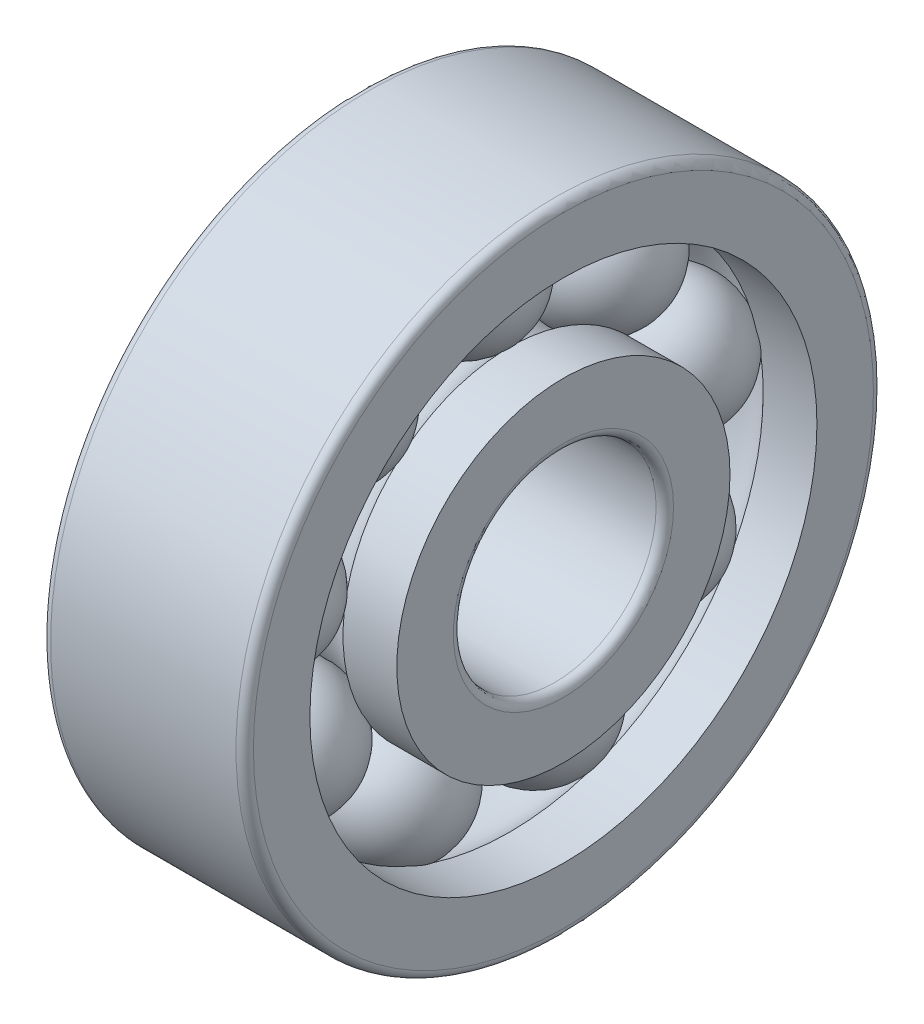
SolidWorks part; units mm, degrees
ref_plane "Plane1" through (0, 0, 0) normal (0, 0, 1) x (1, 0, 0)
ref_plane "Plane2" through (0, 0, 0) normal (0, 1, 0) x (1, 0, 0)
ref_plane "Plane3" through (0, 0, 0) normal (1, 0, 0) x (0, 0, -1)
sketch "Clipboard" plane through (0, 0, 0) normal (0, 0, 1) x (1, 0, 0)
  line L0 (-10, 0) -> (10, 0) construction
  line L1 (0, 0) -> (22.0854, -3.498)
  line L2 (0, 0) -> (7.2489, -0.1265)
  line L3 (0, 0) -> (22.3573, 0.3902)
  line L4 (0, 0) -> (-22.3573, -0.3902)
  dimension "BallCLRad" = 7.25
sketch "CagSpiSke" plane through (0, 0, 0) normal (0, 0, 1) x (1, 0, 0)
  line L0 (0.225, 6.875) -> (0.225, 7.625)
  line L1 (0.225, 7.625) -> (-0.225, 7.625)
  line L2 (-0.225, 7.625) -> (-0.225, 6.875)
  line L3 (-0.225, 6.875) -> (0.225, 6.875)
  line L4 (-20.6375, 0) -> (20.6375, 0) construction
  line L5 (0, 0) -> (0, 23.7692) construction
  dimension "OD" = 15.25
  dimension "ID" = 13.75
revolve "CageSpine" add sketch "CagSpiSke" angle 0.001 about L4 reverse direction yes
ref_axis "Axis1" through (-50, 0, 0) along (1, 0, 0)
sketch "CagBalSke" plane through (0, 0, 0) normal (0, 0, 1) x (1, 0, 0)
  line L0 (-2.475, 7.25) -> (2.475, 7.25)
  line L1 (-1.905, 7.25) -> (1.905, 7.25) construction
  line L2 (-10, 0) -> (10, 0) construction
  line L3 (0, 0) -> (0, 24) construction
  arc A0 (2.475, 7.25) -> (-2.475, 7.25) centre (0, 7.25) cw
  dimension "BallCLRad" = 7.25
revolve "CageBall" [suppressed] add sketch "CagBalSke" angle 360 about L1 reverse direction yes
pattern_circular "CageBalls" [suppressed] count 9 every 40 about axis through (-50, 0, 0) along (1, 0, 0)
sketch "CagTrmODSke" plane through (0, 0, 0) normal (0, 0, 1) x (1, 0, 0)
  line L0 (2.476, 7.625) -> (2.476, 9.726)
  line L1 (2.476, 9.726) -> (-2.476, 9.726)
  line L2 (-2.476, 9.726) -> (-2.476, 7.625)
  line L3 (-2.476, 7.625) -> (2.476, 7.625)
  line L4 (-20.6375, 0) -> (20.6375, 0) construction
  line L5 (0, 0) -> (0, 25) construction
  dimension "Width" = 4.952
  dimension "ID" = 15.25
  dimension "OD" = 19.452
revolve "CageTrimOD" [suppressed] cut sketch "CagTrmODSke" angle 360 about L4 reverse direction yes
sketch "CagTrmIDSke" plane through (0, 0, 0) normal (0, 0, 1) x (1, 0, 0)
  line L0 (2.476, 4.776) -> (2.476, 6.875)
  line L1 (2.476, 6.875) -> (-2.476, 6.875)
  line L2 (-2.476, 6.875) -> (-2.476, 4.776)
  line L3 (-2.476, 4.776) -> (2.476, 4.776)
  line L4 (-20.6375, 0) -> (20.6375, 0) construction
  line L5 (0, 0) -> (0, 25) construction
  dimension "Width" = 4.952
  dimension "ID" = 9.552
  dimension "OD" = 13.75
revolve "CageTrimID" [suppressed] cut sketch "CagTrmIDSke" angle 360 about L4 reverse direction yes
sketch "BalSimSke" plane through (0, 0, 0) normal (0, 0, 1) x (1, 0, 0)
  line L0 (-10, 0) -> (10, 0) construction
  line L1 (-10, 7.25) -> (10, 7.25) construction
  line L2 (0, 0) -> (0, 23) construction
  circle A0 centre (0, 7.25) radius 2.25
  dimension "BallCLRad" = 7.25
  dimension "Ball_diameter" = 4.5
revolve "BallsSimplified" [suppressed] add sketch "BalSimSke" angle 360 about L0
sketch "BalDetSke" plane through (0, 0, 0) normal (0, 0, 1) x (1, 0, 0)
  line L0 (-2.25, 7.25) -> (2.25, 7.25)
  line L1 (-1.905, 7.25) -> (1.905, 7.25) construction
  line L2 (0, 0) -> (0, 25) construction
  arc A0 (2.25, 7.25) -> (-2.25, 7.25) centre (0, 7.25) cw
  dimension "BallCLRad" = 7.25
  dimension "Ball_diameter" = 4.5
revolve "BallDetailed" add sketch "BalDetSke" angle 360 about L1 reverse direction yes
sketch "InnRacSke" plane through (0, 0, 0) normal (0, 0, 1) x (1, 0, 0)
  line L0 (-1.6434, 5.75) -> (-3.5, 5.75)
  line L1 (-3.5, 5.75) -> (-3.5, 3.8)
  line L2 (-3.2, 3.5) -> (3.2, 3.5)
  line L3 (3.5, 3.8) -> (3.5, 5.75)
  line L4 (3.5, 5.75) -> (1.6434, 5.75)
  line L5 (-20.6375, 0) -> (20.6375, 0) construction
  line L6 (0, 0) -> (0, 30) construction
  arc A0 (-3.5, 3.8) -> (-3.2, 3.5) centre (-3.2, 3.8) ccw
  arc A1 (3.2, 3.5) -> (3.5, 3.8) centre (3.2, 3.8) ccw
  arc A2 (1.6434, 5.75) -> (-1.6434, 5.75) centre (0, 7.25) cw
  dimension "BallCLRad" = 7.25
  dimension "Fillet_radius" = 0.3
  dimension "Ball_diameter" = 4.45
  dimension "ID" = 7
  dimension "OD" = 11.5
  dimension "Width" = 7
revolve "InnerRace" add sketch "InnRacSke" angle 360 about L5 reverse direction yes
sketch "OutRacSke" plane through (0, 0, 0) normal (0, 0, 1) x (1, 0, 0)
  line L0 (-1.6434, 8.75) -> (-3.5, 8.75)
  line L1 (-3.5, 8.75) -> (-3.5, 10.7)
  line L2 (-3.2, 11) -> (3.2, 11)
  line L3 (3.5, 10.7) -> (3.5, 8.75)
  line L4 (3.5, 8.75) -> (1.6434, 8.75)
  line L5 (-20.6375, 0) -> (20.6375, 0) construction
  line L6 (0, 0) -> (0, 30) construction
  arc A0 (-3.5, 10.7) -> (-3.2, 11) centre (-3.2, 10.7) cw
  arc A1 (3.2, 11) -> (3.5, 10.7) centre (3.2, 10.7) cw
  arc A2 (1.6434, 8.75) -> (-1.6434, 8.75) centre (0, 7.25) ccw
  dimension "BallCLRad" = 7.25
  dimension "Fillet_radius" = 0.3
  dimension "Ball_diameter" = 4.45
  dimension "Width" = 7
revolve "OuterRace" add sketch "OutRacSke" angle 360 about L5 reverse direction yes
pattern_circular "BallsDetailed" count 9 every 40 about axis through (-50, 0, 0) along (1, 0, 0) of "BallDetailed"
equation "\"BallCLRad@Clipboard\" = ( \"OD@OutRacSke\" + \"ID@InnRacSke\" ) / 4"
equation "\"BallCLRad@BalSimSke\" = \"BallCLRad@Clipboard\""
equation "\"BallCLRad@BalDetSke\" = \"BallCLRad@Clipboard\""
equation "\"BallCLRad@InnRacSke\" = \"BallCLRad@Clipboard\""
equation "\"BallCLRad@OutRacSke\" = \"BallCLRad@Clipboard\""
equation "\"Ball_diameter@InnRacSke\" = \"Ball_diameter@BalDetSke\" - 0.05"
equation "\"Ball_diameter@OutRacSke\" = \"Ball_diameter@BalDetSke\" - 0.05"
equation "\"Ball_diameter@BalSimSke\" = \"Ball_diameter@BalDetSke\""
equation "\"Width@OutRacSke\" = \"Width@InnRacSke\""
equation "\"Fillet_radius@OutRacSke\" = \"Fillet_radius@InnRacSke\""
equation "\"Max_count@Clipboard\" = int( 3.14159265 / atn(( \"Ball_diameter@BalDetSke\" / 2) / sqr( \"BallCLRad@Clipboard\"  *  \"BallCLRad@Clipboard\" - ( \"Ball_diameter@BalDetSke\" / 2) *  ( \"Ball_diameter@BalDetSke\" / 2))))"
equation "\"Max_count@Clipboard\" = ((sgn( \"Max_count@Clipboard\" - \"Count@Clipboard\" )-1)*( \"Max_count@Clipboard\" - \"Count@Clipboard\" ))/-2+ \"Count@Clipboard\""
equation "\"Count@BallsDetailed\" = int( \"Show_count@Clipboard\" ) "
equation "\"Count@BallsDetailed\" = ((sgn( \"Count@BallsDetailed\" - \"Max_count@Clipboard\" )-1)*( \"Count@BallsDetailed\" - \"Max_count@Clipboard\" ))/-2+ \"Max_count@Clipboard\""
equation "\"Count@BallsDetailed\" = ((sgn( \"Count@BallsDetailed\" - \"Min_count@Clipboard\" )+1)*( \"Count@BallsDetailed\" - \"Min_count@Clipboard\"))/2 +\"Min_count@Clipboard\""
equation "\"Angle@BallsDetailed\" = 360.0 / \"Max_count@Clipboard\""
equation "\"BallCLRad@CagBalSke\" = \"BallCLRad@Clipboard\""
equation "\"Count@CageBalls\" = \"Count@BallsDetailed\""
equation "\"Angle@CageBalls\" = \"Angle@BallsDetailed\""
equation "\"Angle@CageSpine\" =  \"Angle@CageBalls\" * ( \"Count@CageBalls\" -1 + int( \"Count@CageBalls\" / \"Max_count@Clipboard\" ) )  + 0.001 -  int( \"Count@CageBalls\" / \"Max_count@Clipboard\" ) * 0.001"
equation "\"Angle@CageSpine\" =  \"Angle@CageSpine\" * int( \"Min_count@Clipboard\" / 2) + int(1 / \"Min_count@Clipboard\")  * 0.001"
equation "\"CageWallOD@CagBalSke\" =  \"Ball_diameter@BalDetSke\" * 1.1"
equation "\"Thickness@CagSpiSke\" =  \"Ball_diameter@BalDetSke\" * 0.1"
equation "\"OD@CagTrmODSke\" = \"BallCLRad@Clipboard\" * 2 + \"CageWallOD@CagBalSke\" + 0.002"
equation "\"ID@CagTrmODSke\" = \"BallCLRad@Clipboard\" * 2 + \"Ball_diameter@BalDetSke\" / 6"
equation "\"OD@CagTrmIDSke\" = \"BallCLRad@Clipboard\" * 2 - \"Ball_diameter@BalDetSke\" / 6"
equation "\"ID@CagTrmIDSke\" = \"BallCLRad@Clipboard\" * 2 - \"CageWallOD@CagBalSke\" + 0.002"
equation "\"OD@CagSpiSke\" = \"ID@CagTrmODSke\""
equation "\"ID@CagSpiSke\" = \"OD@CagTrmIDSke\""
equation "\"Width@CagTrmODSke\" = \"CageWallOD@CagBalSke\" + 0.002"
equation "\"Width@CagTrmIDSke\" = \"CageWallOD@CagBalSke\" + 0.002"
